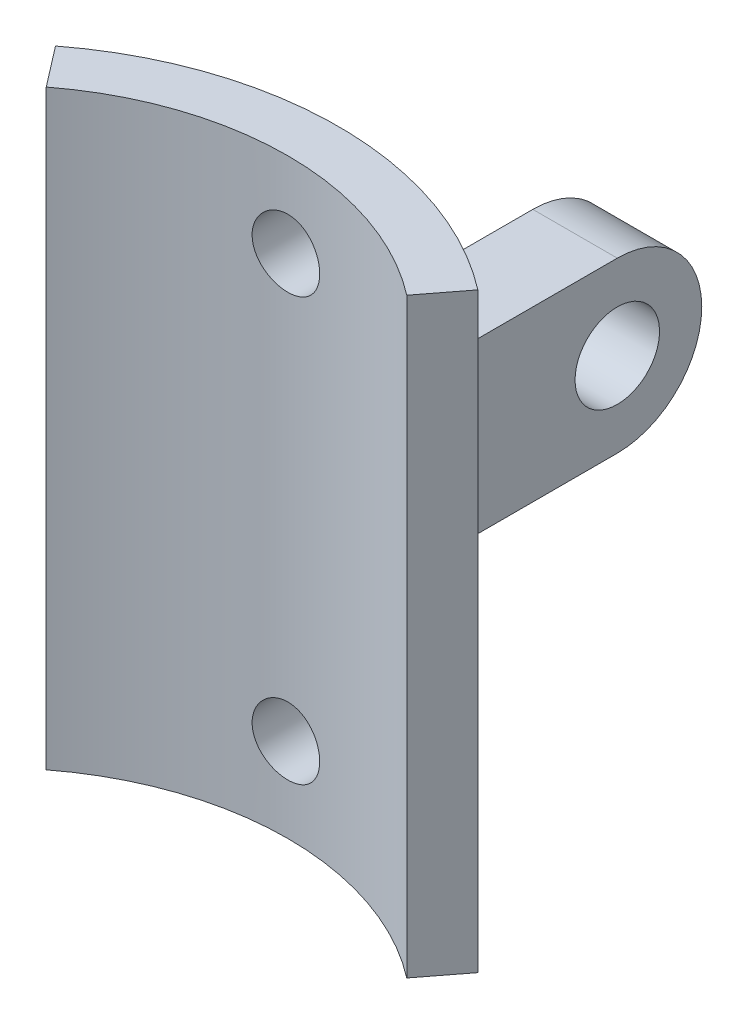
SolidWorks part; units mm, degrees
ref_plane "Front Plane" through (0, 0, 0) normal (0, 0, 1) x (1, 0, 0)
ref_plane "Top Plane" through (0, 0, 0) normal (0, 1, 0) x (1, 0, 0)
ref_plane "Right Plane" through (0, 0, 0) normal (1, 0, 0) x (0, 0, -1)
sketch "Sketch2" plane through (0, 0, 0) normal (0, 1, 0) x (1, 0, 0)
  circle A0 centre (0, 0) radius 17.5
  circle A1 centre (0, 0) radius 20.5
  dimension "D1" = 35
  dimension "D2" = 3
extrude "Boss-Extrude1" add sketch "Sketch2" along normal blind 35
sketch "Sketch3" plane through (0, 35, 0) normal (0, 1, 0) x (1, 0, 0)
  line L0 (0, 0) -> (12.5, 16.2481)
  line L1 (0, 0) -> (-12.5, 16.2481)
  line L2 (12.5, 16.2481) -> (-12.5, 16.2481) construction
  circle A0 centre (0, 0) radius 20.5 construction
  arc A1 (12.5, 16.2481) -> (-12.5, 16.2481) centre (0, 0) ccw
  point P6 (0, 20.5)
  dimension "D1" = 25
extrude "Cut-Extrude1" cut sketch "Sketch3" against normal through all flip side to cut
sketch "Sketch5" plane through (0, 0, 0) normal (0, 0, 1) x (1, 0, 0)
  line L0 (10.6707, 35) -> (-10.6707, 35) construction
  line L1 (-10.6707, 0) -> (10.6707, 0) construction
  circle A0 centre (0, 30) radius 2
  circle A1 centre (0, 5) radius 2
  dimension "D1" = 4
  dimension "D2" = 5
  dimension "D3" = 5
extrude "Cut-Extrude2" cut sketch "Sketch5" against normal through all
ref_plane "Plane1" through (0, 17.5, 0) normal (0, 1, 0) x (1, 0, 0)
sketch "Sketch7" plane through (0, 15, 0) normal (-1, 0, 0) x (0, 1, 0)
  line L2 (-2.5, 34.5) -> (-2.5, 18.5)
  line L4 (7.5, 34.5) -> (7.5, 18.5)
  line L5 (13, 20.5) -> (-8, 20.5) construction
  line L7 (-2.5, 18.5) -> (7.5, 18.5)
  line L8 (-8, 20.5) -> (13, 20.5) construction
  arc A3 (7.5, 34.5) -> (-2.5, 34.5) centre (2.5, 34.5) ccw
  point P6 (2.5, 18.5)
  point P8 (2.5, 20.5)
  dimension "D1" = 10
  dimension "D2" = 16
  dimension "D3" = 2
extrude "Boss-Extrude2" add sketch "Sketch7" along normal blind 2.5 and the other way blind 2.5
sketch "Sketch9" plane through (0, 17.5, 0) normal (0, 1, 0) x (1, 0, 0)
  arc A0 (12.5, 16.2481) -> (-12.5, 16.2481) centre (0, 0) ccw construction
  point P0 (0, 20.5)
sketch "Sketch10" plane through (-2.5, 0, 0) normal (-1, 0, 0) x (0, 1, 0)
  circle A0 centre (17.5, 34.5) radius 2.5
  arc A3 (22.5, 34.5) -> (12.5, 34.5) centre (17.5, 34.5) ccw construction
  dimension "D1" = 5
extrude "Cut-Extrude3" cut sketch "Sketch10" against normal through all
fillet "Fillet2" radius 2 4 edges at (-2.5, 17.5, -20.347) (0, 22.5, -20.5) (2.5, 17.5, -20.347) (0, 12.5, -20.5)
